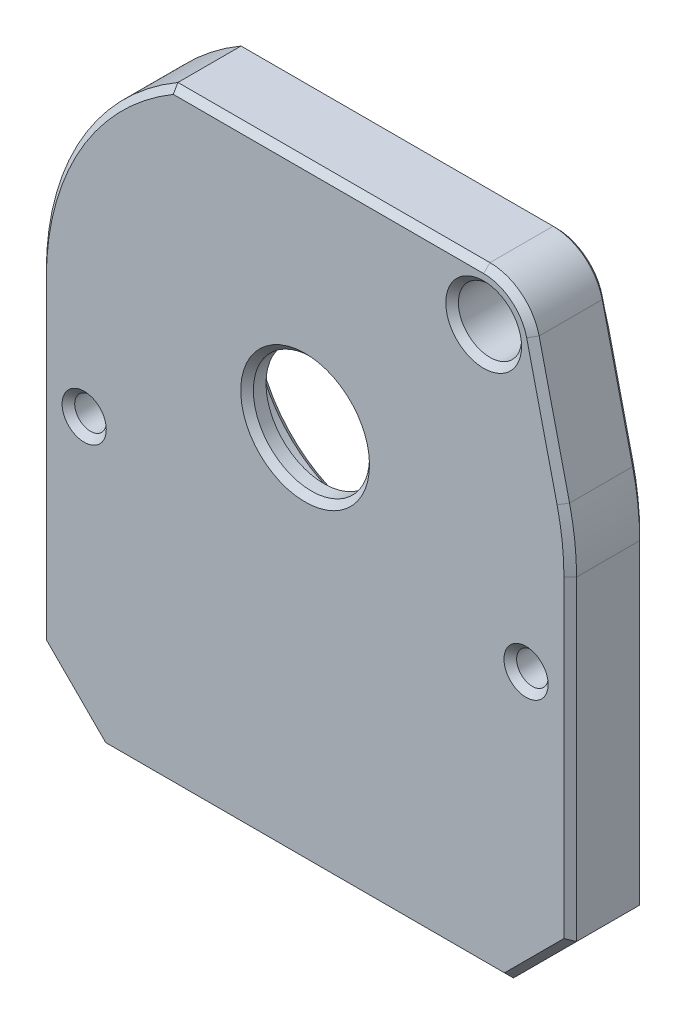
SolidWorks part; units mm, degrees
material "6061-T6 (GB)"
ref_plane "前视" through (0, 0, 0) normal (0, 0, 1) x (1, 0, 0)
ref_plane "上视" through (0, 0, 0) normal (0, 1, 0) x (1, 0, 0)
ref_plane "右视" through (0, 0, 0) normal (1, 0, 0) x (0, 0, -1)
sketch "草图1" plane through (0, 0, 0) normal (0, 0, 1) x (1, 0, 0)
  line L0 (0, 0) -> (0, -29.4586) construction
  line L1 (-21, 0) -> (-21, -25)
  line L2 (-16, -30) -> (16, -30)
  line L3 (21, -25) -> (21, 0)
  line L4 (0, 0) -> (22.58, 22.58) construction
  line L5 (-10.5765, 18.1421) -> (14.1421, 18.1421)
  line L6 (18.0363, 15.0563) -> (20.4442, 4.7995)
  line L7 (-21, -25) -> (-16, -30)
  line L8 (16, -30) -> (21, -25)
  circle A0 centre (0, 0) radius 4.6
  arc A1 (21, 0) -> (20.4442, 4.7995) centre (0, 0) ccw
  arc A2 (18.0363, 15.0563) -> (14.1421, 18.1421) centre (14.1421, 14.1421) ccw
  arc A3 (-10.5765, 18.1421) -> (-21, 0) centre (0, 0) ccw
  circle A4 centre (14.1421, 14.1421) radius 2.5
  circle A5 centre (-17.5, -8) radius 1.25
  circle A6 centre (17.5, -8) radius 1.25
  point P6 (-21, -30)
  point P8 (21, -30)
  dimension "D1" = 9.2
  dimension "D2" = 30
  dimension "D4" = 45
  dimension "D5" = 20
  dimension "D6" = 8
  dimension "D7" = 18.1421
  dimension "D8" = 5
  dimension "D9" = 8
  dimension "D10" = 35
  dimension "D13" = 2.5
  dimension "D3" = 42
extrude "凸台-拉伸1" add sketch "草图1" along normal blind 6
sketch "草图2" plane through (0, 0, 0) normal (0, 0, -1) x (-1, 0, 0)
  circle A0 centre (0, 0) radius 9.5
  dimension "D1" = 19
extrude "切除-拉伸1" cut sketch "草图2" against normal blind 4
sketch "草图3" plane through (0, 0, 4) normal (0, 0, -1) x (-1, 0, 0)
  circle A0 centre (0, 0) radius 8
  dimension "D1" = 16
extrude "切除-拉伸2" cut sketch "草图3" against normal blind 0.5
sketch "草图4" plane through (0, -30, 0) normal (0, -1, 0) x (1, 0, 0)
  line L0 (-21, 3) -> (21, 3) construction
  line L1 (-21, 6) -> (-21, 0) construction
  line L2 (21, 6) -> (21, 0) construction
  line L3 (0, 0) -> (0, 9.1819) construction
  circle A0 centre (-10, 3) radius 1.25
  circle A1 centre (10, 3) radius 1.25
  dimension "D1" = 2.5
  dimension "D2" = 20
extrude "切除-拉伸3" cut sketch "草图4" against normal blind 8
sketch "草图5" plane through (0, 0, 0) normal (0, 0, -1) x (-1, 0, 0)
  circle A0 centre (-14.1421, 14.1421) radius 3.5
  dimension "D1" = 7
extrude "切除-拉伸4" cut sketch "草图5" against normal blind 1
chamfer "倒角1" distance 0.5 angle 45 29 edges at (-21, -12.5, 0) (-18.5, -27.5, 0) (0, -30, 0) (18.5, -27.5, 0) (21, -12.5, 0) (20.8606, 2.4158, 0) (19.2402, 9.9279, 0) (16.6264, 17.2772, 0) (1.7828, 18.1421, 0) (-18.2086, 10.4617, 0) (-9.5, 0, 0) (16.6421, 14.1421, 6) (1.7828, 18.1421, 6) (16.6264, 17.2772, 6) (19.2402, 9.9279, 6) (20.8606, 2.4158, 6) (21, -12.5, 6) (18.5, -27.5, 6) (0, -30, 6) (-18.5, -27.5, 6) (-21, -12.5, 6) (-18.2086, 10.4617, 6) (4.6, 0, 6) (16.25, -8, 0) (-16.25, -8, 0) (16.25, -8, 6) (-16.25, -8, 6) (10.6421, 14.1421, 0) (11.6421, 14.1421, 1)
